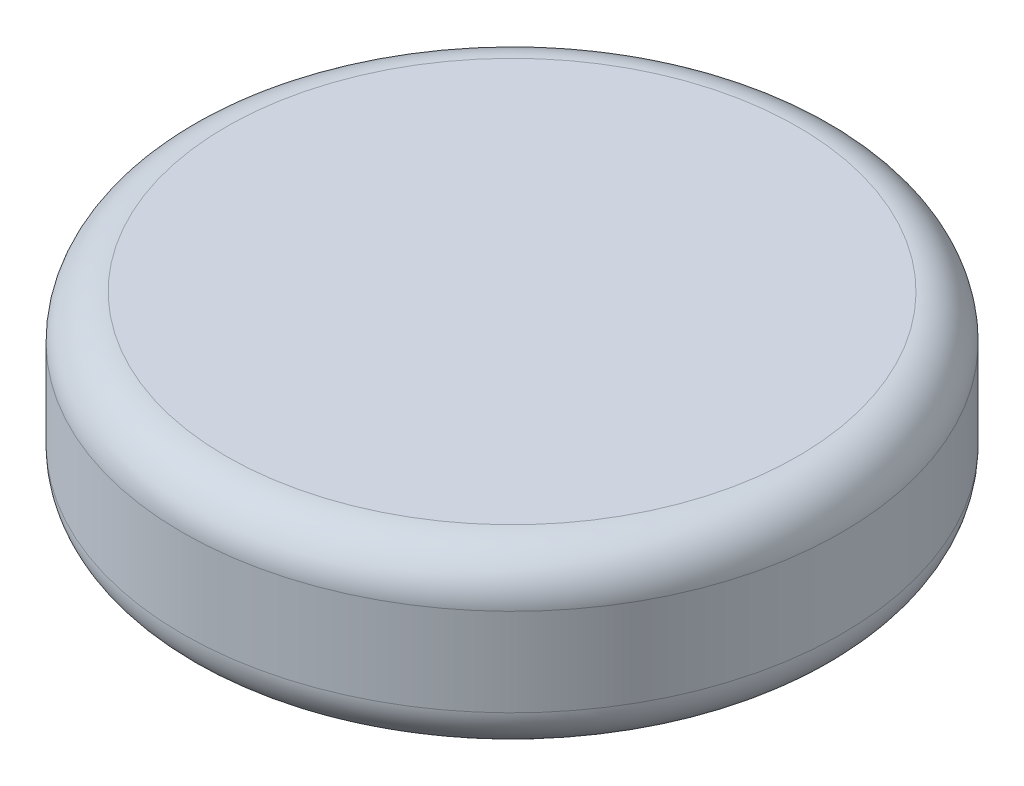
SolidWorks part; units mm, degrees
ref_plane "Спереди" through (0, 0, 0) normal (0, 0, 1) x (1, 0, 0)
ref_plane "Сверху" through (0, 0, 0) normal (0, 1, 0) x (1, 0, 0)
ref_plane "Справа" through (0, 0, 0) normal (1, 0, 0) x (0, 0, -1)
other "Configuration Table"
sketch "Эскиз1" plane through (0, 0, 0) normal (0, 1, 0) x (1, 0, 0)
  line L1 (3.1, -3.1) -> (-3.1, -3.1)
  line L2 (3.1, -3.1) -> (3.1, 3.1)
  line L3 (3.1, 3.1) -> (-3.1, 3.1)
  line L4 (-3.1, -3.1) -> (-3.1, 3.1)
  line L5 (3.1, -3.1) -> (-3.1, 3.1) construction
  line L6 (3.1, 3.1) -> (-3.1, -3.1) construction
  line L7 (1.9, -1.9) -> (-1.9, -1.9)
  line L8 (1.9, -1.9) -> (1.9, 1.9)
  line L9 (1.9, 1.9) -> (-1.9, 1.9)
  line L10 (-1.9, -1.9) -> (-1.9, 1.9)
  line L11 (1.9, -1.9) -> (-1.9, 1.9) construction
  line L12 (1.9, 1.9) -> (-1.9, -1.9) construction
  circle A0 centre (0, 0) radius 7.5
  circle A1 centre (0, 0) radius 6.3
  point P13 (1.9, 0)
  dimension "D4" = 15
  dimension "D5" = 1.2
  dimension "D1" = 3.8
  dimension "D2" = 1.2
extrude "Бобышка-Вытянуть1" add sketch "Эскиз1" against normal blind 1.2 contours A1 L1 L4 L3 L2 | A0 A1 | L10 L7 L8 L9 | L4 L1 L2 L3 L7 L10 L9 L8 region at (0, 0, 3.0123) region at (0, 0, 0) region at (-7.2879, 0, 0) region at (-6.1218, 0, 0)
extrude "Бобышка-Вытянуть2" add sketch "Эскиз1<3>" against normal blind 4 contours A0 A1 region at (-7.2879, 0, 0)
sketch "Эскиз1<3>" plane through (0, 0, 0) normal (0, 1, 0) x (1, 0, 0) same geometry as "Эскиз1"
extrude "Бобышка-Вытянуть3" add sketch "Эскиз1<5>" against normal blind 2 contours L4 L1 L2 L3 L7 L10 L9 L8 | L10 L7 L8 L9 region at (0, 0, 3.0123) region at (0, 0, 0)
sketch "Эскиз1<5>" plane through (0, 0, 0) normal (0, 1, 0) x (1, 0, 0) same geometry as "Эскиз1"
extrude "Бобышка-Вытянуть4" add sketch "Эскиз1<6>" against normal blind 3 from surface contours L4 L1 L2 L3 L7 L10 L9 L8 region at (0, 0, 3.0123) starting at face at (0, -2, 0)
sketch "Эскиз1<6>" plane through (0, 0, 0) normal (0, 1, 0) x (1, 0, 0) same geometry as "Эскиз1"
fillet "Скругление1" radius 1 2 edges at (0, -4, 7.5) (0, 0, 7.5)
sketch "Эскиз2" plane through (0, -5, 0) normal (0, -1, 0) x (1, 0, 0)
  line L1 (1.9, -1.9) -> (-1.9, -1.9)
  line L2 (1.9, -1.9) -> (1.9, 1.9)
  line L3 (1.9, 1.9) -> (-1.9, 1.9)
  line L4 (-1.9, -1.9) -> (-1.9, 1.9)
  line L5 (1.9, -1.9) -> (-1.9, 1.9) construction
  line L6 (1.9, 1.9) -> (-1.9, -1.9) construction
  line L7 (1.7, -1.7) -> (-1.7, -1.7)
  line L8 (1.7, -1.7) -> (1.7, 1.7)
  line L9 (1.7, 1.7) -> (-1.7, 1.7)
  line L10 (-1.7, -1.7) -> (-1.7, 1.7)
  line L11 (1.7, -1.7) -> (-1.7, 1.7) construction
  line L12 (1.7, 1.7) -> (-1.7, -1.7) construction
  point P0 (0, 0)
  point P7 (0, 0)
  dimension "D1" = 0.2
extrude "Бобышка-Вытянуть5" add sketch "Эскиз2" against normal blind 0.8
